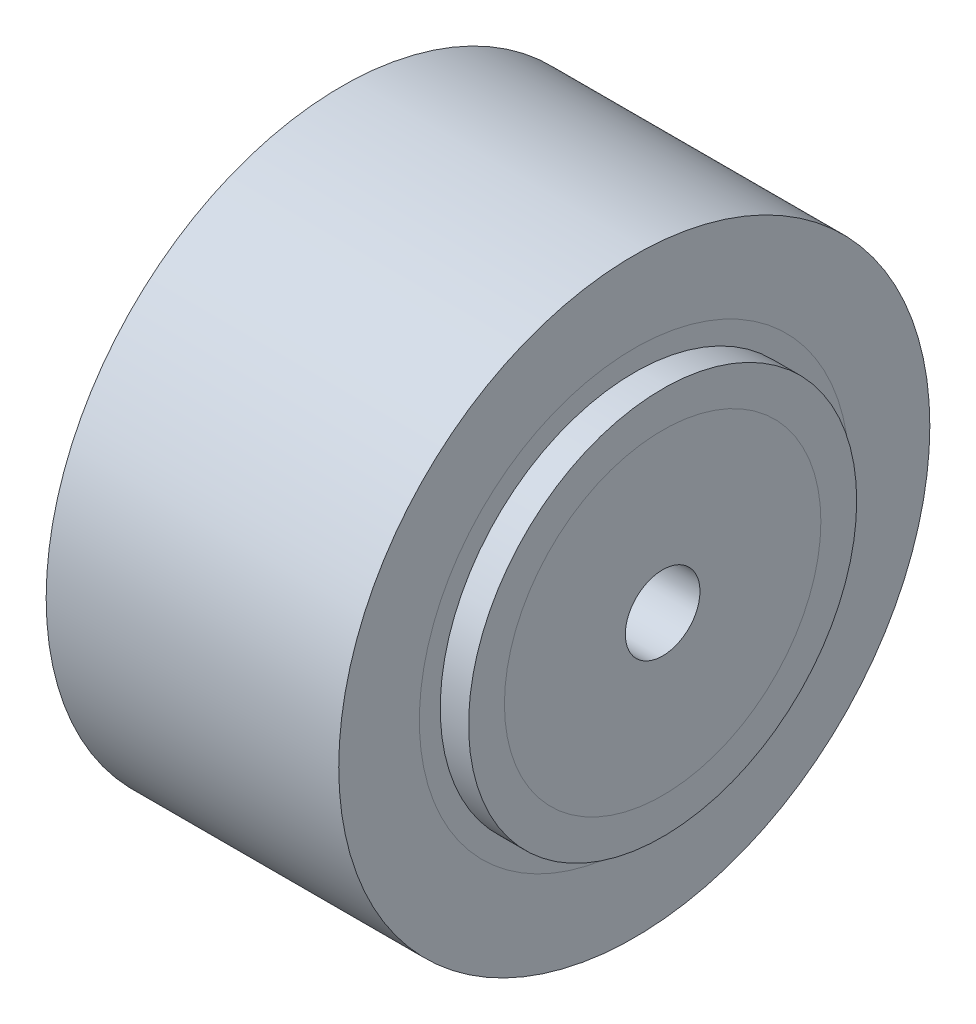
SolidWorks part; units mm, degrees
ref_plane "Front Plane" through (0, 0, 0) normal (0, 0, 1) x (1, 0, 0)
ref_plane "Top Plane" through (0, 0, 0) normal (0, 1, 0) x (1, 0, 0)
ref_plane "Right Plane" through (0, 0, 0) normal (1, 0, 0) x (0, 0, -1)
sketch "Sketch1" plane through (0, 0, 0) normal (1, 0, 0) x (0, 0, -1)
  circle A0 centre (0, 0) radius 19.8
  circle A1 centre (0, 0) radius 14.4
  circle A2 centre (0, 0) radius 13
  circle A3 centre (0, 0) radius 2.5
  circle A4 centre (0, 0) radius 10.6
  dimension "D1" = 39.6
  dimension "D3" = 26
  dimension "D4" = 5
  dimension "D5" = 21.2
  dimension "D2" = 28.8
extrude "Boss-Extrude4" add sketch "Sketch1" along normal blind 9.8 contours A0 A1 region at (0, 0, 19.24)
extrude "Boss-Extrude5" add sketch "Sketch1<6>" along normal blind 9.8 separate body contours A1 A2 region at (0, 0, 13.9927)
sketch "Sketch1<6>" plane through (0, 0, 0) normal (1, 0, 0) x (0, 0, -1) same geometry as "Sketch1"
extrude "Boss-Extrude6" add sketch "Sketch1<7>" along normal blind 11.7 separate body contours A2 A4 region at (0, 0, 12.6323)
sketch "Sketch1<7>" plane through (0, 0, 0) normal (1, 0, 0) x (0, 0, -1) same geometry as "Sketch1"
extrude "Boss-Extrude7" add sketch "Sketch1<8>" along normal blind 11.7 separate body contours A4 A3 region at (0, 0, 10.3002)
sketch "Sketch1<8>" plane through (0, 0, 0) normal (1, 0, 0) x (0, 0, -1) same geometry as "Sketch1"
mirror "Mirror3" about plane through (0, 0, 0) normal (1, 0, 0) of "Boss-Extrude4"
sketch "Sketch2" plane through (0, 0, 0) normal (-1, 0, 0) x (0, 0, 1)
  circle A1 centre (0, 0) radius 14.4
  circle A2 centre (0, 0) radius 14.4
  circle M2 centre (0, 0) radius 13
  circle M3 centre (0, 0) radius 14.4
  dimension "D1" = 0
extrude "Boss-Extrude8" add sketch "Sketch2" along normal up to surface (9.8 mm away) separate body contours M3 M2 region at (0, 0, -13.9927) up to face at (-9.8, 0, -14.4)
sketch "Sketch3" plane through (0, 0, 0) normal (-1, 0, 0) x (0, 0, 1)
  circle A1 centre (0, 0) radius 13
  circle A2 centre (0, 0) radius 13
  circle M2 centre (0, 0) radius 10.6
  circle M3 centre (0, 0) radius 13
  dimension "D1" = 0
extrude "Boss-Extrude9" add sketch "Sketch3" along normal blind 11.7 separate body contours M3 M2 region at (0, 0, -12.6323)
sketch "Sketch4" plane through (0, 0, 0) normal (-1, 0, 0) x (0, 0, 1)
  circle A1 centre (0, 0) radius 10.6
  circle A2 centre (0, 0) radius 10.6
  circle M2 centre (0, 0) radius 2.5
  circle M3 centre (0, 0) radius 10.6
  dimension "D1" = 0
extrude "Boss-Extrude10" add sketch "Sketch4" along normal blind 11.7 separate body contours M3 M2 region at (0, 0, -10.3002)
